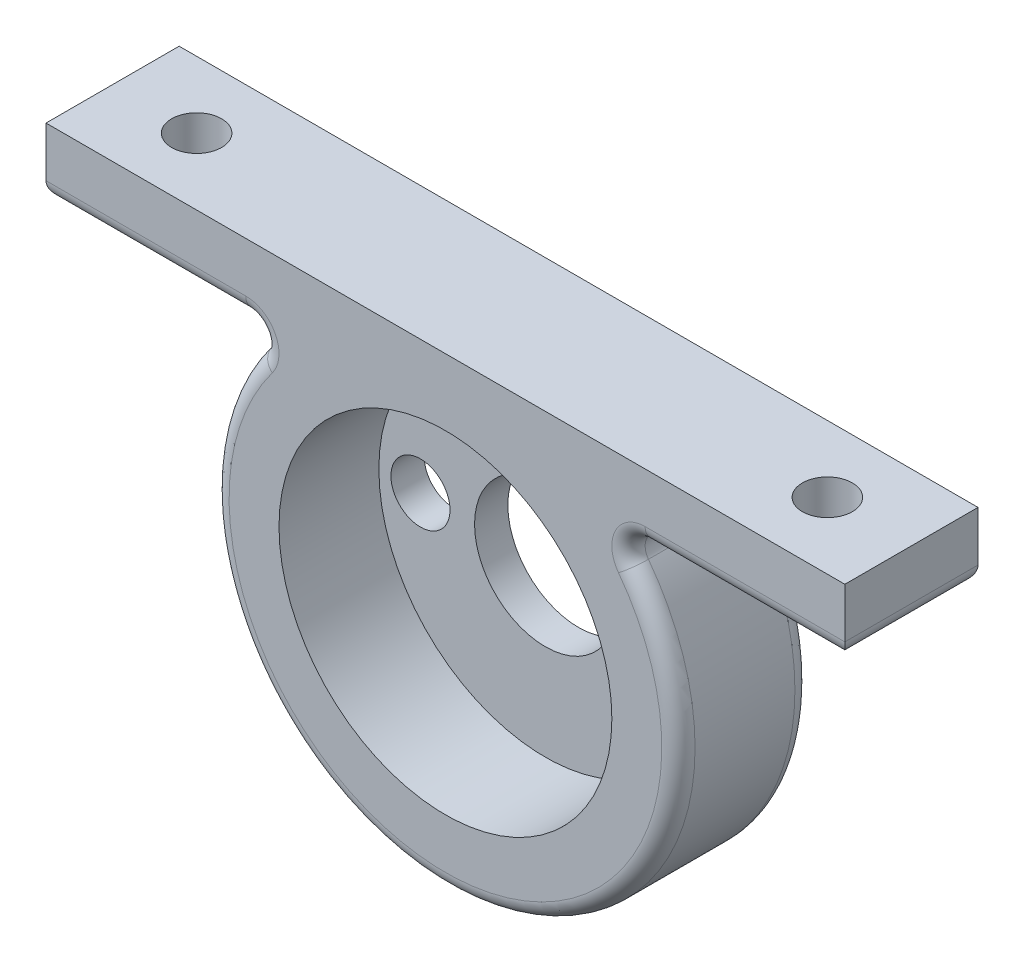
SolidWorks part; units mm, degrees
material "ABS"
ref_plane "Alzado" through (0, 0, 0) normal (0, 0, 1) x (1, 0, 0)
ref_plane "Planta" through (0, 0, 0) normal (0, 1, 0) x (1, 0, 0)
ref_plane "Vista lateral" through (0, 0, 0) normal (1, 0, 0) x (0, 0, -1)
sketch "Croquis1" plane through (0, 0, 0) normal (0, 0, 1) x (1, 0, 0)
  line L0 (0, 14) -> (24, 14)
  line L1 (0, 14) -> (-24, 14)
  line L2 (-24, 14) -> (-24, 10)
  line L3 (-24, 10) -> (-9.798, 10)
  line L4 (24, 14) -> (24, 10)
  line L5 (24, 10) -> (9.798, 10)
  arc A1 (-9.798, 10) -> (9.798, 10) centre (0, 0) ccw
  dimension "D1" = 14
  dimension "D2" = 14
  dimension "D3" = 48
  dimension "D5" = 4
  dimension "D6" = 4
  dimension "D7" = 24
extrude "Saliente-Extruir1" add sketch "Croquis1" along normal blind 8
fillet "Redondeo1" radius 1 10 edges at (-16.899, 10, 8) (-16.899, 10, 0) (16.899, 10, 8) (16.899, 10, 0) (-9.798, 10, 4) (0, -14, 8) (9.798, 10, 4) (0, -14, 0) (24, 10, 4) (-24, 10, 4)
sketch "Croquis2" plane through (0, 10, 0) normal (0, -1, 0) x (1, 0, 0)
  line L0 (23, 1) -> (23, 7) construction
  line L2 (12, 1) -> (23, 1) construction
  line L4 (-23, 1) -> (-12, 1) construction
  line L5 (-23, 7) -> (-23, 1) construction
  circle A0 centre (-18.9495, 4) radius 1.5
  circle A1 centre (18.9495, 4) radius 1.5
  dimension "D1" = 3
  dimension "D2" = 3
  dimension "D3" = 4.0505
  dimension "D4" = 3
  dimension "D5" = 3
  dimension "D6" = 4.0505
extrude "Cortar-Extruir1" cut sketch "Croquis2" against normal through all
sketch "Croquis3" plane through (0, 0, 8) normal (0, 0, 1) x (1, 0, 0)
  circle A0 centre (0, 0) radius 10
  dimension "D1" = 20
extrude "Cortar-Extruir2" cut sketch "Croquis3" against normal blind 6
sketch "Croquis4" plane through (0, 0, 0) normal (0, 0, -1) x (-1, 0, 0)
  line L0 (-24, 14) -> (24, 14) construction
  circle A0 centre (0, 0) radius 4.25
  circle A1 centre (7.5, 0) radius 1.775
  circle A2 centre (-7.5, 0) radius 1.775
  dimension "D1" = 8.5
  dimension "D2" = 7.5
  dimension "D3" = 7.5
  dimension "D4" = 3.55
  dimension "D5" = 3.55
  dimension "D6" = 14
  dimension "D7" = 14
extrude "Cortar-Extruir3" cut sketch "Croquis4" against normal through all
